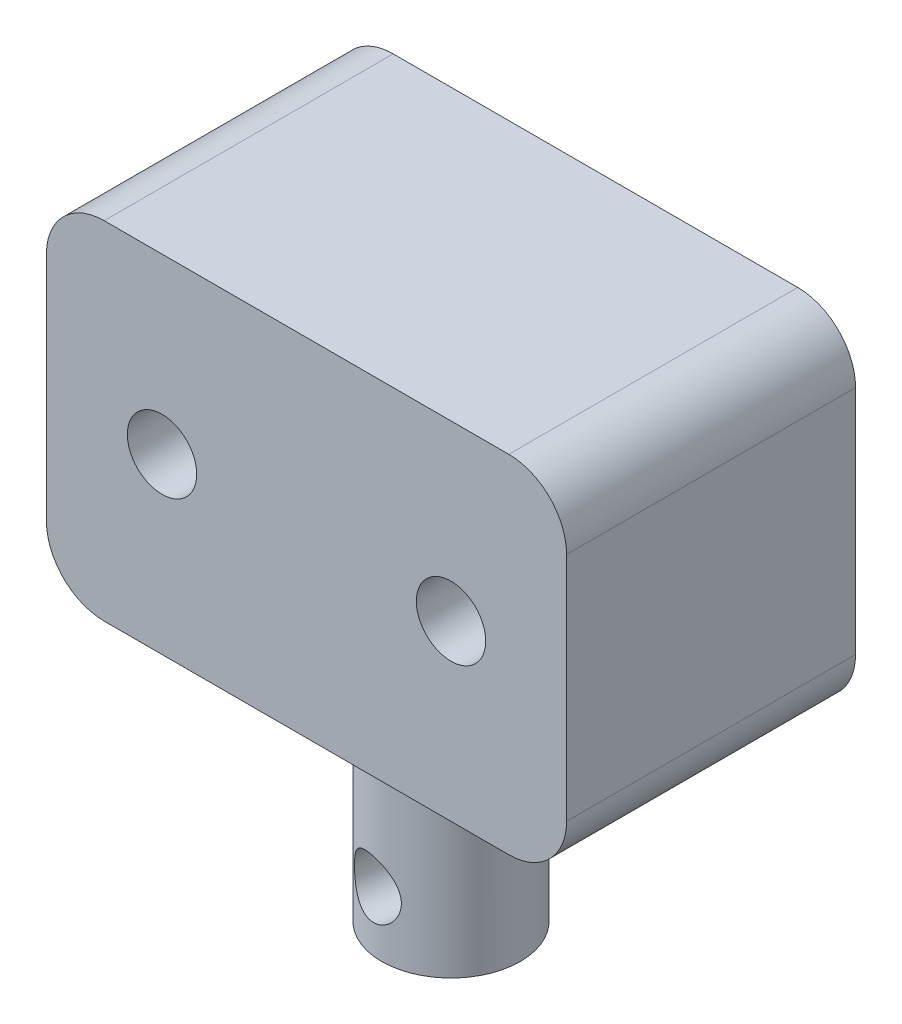
SolidWorks part; units mm, degrees
material "普通碳钢"
ref_plane "前视基准面" through (0, 0, 0) normal (0, 0, 1) x (1, 0, 0)
ref_plane "上视基准面" through (0, 0, 0) normal (0, 1, 0) x (1, 0, 0)
ref_plane "右视基准面" through (0, 0, 0) normal (1, 0, 0) x (0, 0, -1)
sketch "草图1" plane through (0, 0, 0) normal (0, 0, 1) x (1, 0, 0)
  line L0 (-22.5, 0) -> (22.5, 0) construction
  line L1 (-22.5, -15) -> (22.5, -15)
  line L2 (-22.5, -15) -> (-22.5, 15)
  line L3 (-22.5, 15) -> (22.5, 15)
  line L4 (22.5, -15) -> (22.5, 15)
  line L5 (-22.5, -15) -> (22.5, 15) construction
  line L6 (-22.5, 15) -> (22.5, -15) construction
  line L7 (0, 15) -> (0, -15) construction
  circle A0 centre (-12.5, 0) radius 3
  circle A1 centre (12.5, 0) radius 3
  point P0 (0, 0)
  dimension "D3" = 6
  dimension "D1" = 45
  dimension "D2" = 30
  dimension "D4" = 25
extrude "凸台-拉伸1" add sketch "草图1" along normal blind 25
fillet "圆角1" radius 5 4 edges at (22.5, 15, 12.5) (22.5, -15, 12.5) (-22.5, -15, 12.5) (-22.5, 15, 12.5)
sketch "草图2" plane through (0, -15, 0) normal (0, -1, 0) x (1, 0, 0)
  line L0 (-17.5, 12.5) -> (17.5, 12.5) construction
  line L1 (-17.5, 25) -> (-17.5, 0) construction
  line L2 (17.5, 0) -> (17.5, 25) construction
  line L3 (0, 25) -> (0, 0) construction
  line L4 (-17.5, 25) -> (17.5, 25) construction
  circle A0 centre (0, 12.5) radius 6
  dimension "D1" = 12
extrude "凸台-拉伸2" add sketch "草图2" along normal blind 20 contours A0
ref_axis "基准轴1" through (0, -35, 12.5) along (0, 1, 0)
ref_plane "基准面1" through (-2.1376, 0, 12.1231) normal (0.1736, 0, -0.9848) x (-0.9848, 0, -0.1736)
sketch "草图3" plane through (-2.1376, 0, 12.1231) normal (0.1736, 0, -0.9848) x (-0.9848, 0, -0.1736)
  line L0 (-2.1706, -35) -> (-2.1706, -15) construction
  line L1 (-8.1706, -35) -> (3.8294, -35) construction
  line L2 (-8.1706, -15) -> (3.8294, -15) construction
  circle A0 centre (-2.1706, -30) radius 2.5
  dimension "D1" = 5
  dimension "D2" = 5
extrude "切除-拉伸1" cut sketch "草图3" against normal through all and the other way through all contours A0
